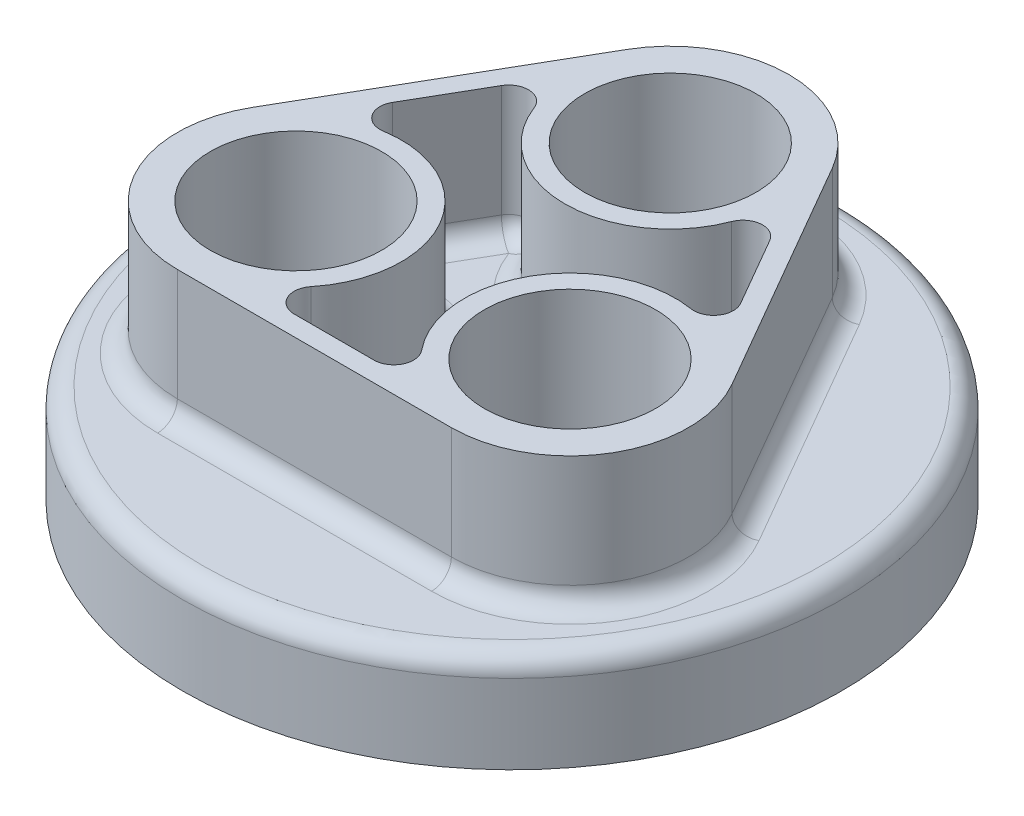
SolidWorks part; units mm, degrees
ref_plane "Front Plane" through (0, 0, 0) normal (0, 0, 1) x (1, 0, 0)
ref_plane "Top Plane" through (0, 0, 0) normal (0, 1, 0) x (1, 0, 0)
ref_plane "Right Plane" through (0, 0, 0) normal (1, 0, 0) x (0, 0, -1)
sketch "Sketch1" plane through (0, 0, 0) normal (0, 1, 0) x (1, 0, 0)
  circle A0 centre (0, 0) radius 50
  dimension "D1" = 100
extrude "Boss-Extrude1" add sketch "Sketch1" along normal blind 15
shell "Shell1" thickness 3 removed face at (0, 0, 50)
sketch "Sketch2" plane through (0, 15, 0) normal (0, 1, 0) x (1, 0, 0)
  line L0 (0, 5.7923) -> (0, 25.3037) construction
  line L1 (-15.5885, 33) -> (-36.3731, -3)
  line L2 (-20.7846, -30) -> (20.7846, -30)
  line L3 (-20.3558, 18.7426) -> (-26.4095, 8.2574)
  line L4 (6.0537, -27) -> (-6.0537, -27)
  line L5 (20.3558, 18.7426) -> (26.4095, 8.2574)
  line L6 (15.5885, 33) -> (36.3731, -3)
  arc A0 (15.5885, 33) -> (-15.5885, 33) centre (0, 24) ccw
  arc A1 (-36.3731, -3) -> (-20.7846, -30) centre (-20.7846, -12) ccw
  circle A2 centre (0, 0) radius 24 construction
  circle A3 centre (0, 24) radius 13
  circle A4 centre (20.7846, -12) radius 13
  circle A5 centre (-20.7846, -12) radius 13
  arc A6 (-23.3335, 3.7957) -> (-8.3796, -22.1053) centre (-20.7846, -12) cw
  arc A7 (-14.9539, 18.3096) -> (14.9539, 18.3096) centre (0, 24) ccw
  arc A8 (-6.0537, -27) -> (-8.3796, -22.1053) centre (-6.0537, -24) cw
  arc A9 (-20.3558, 18.7426) -> (-14.9539, 18.3096) centre (-17.7578, 17.2426) cw
  arc A10 (-26.4095, 8.2574) -> (-23.3335, 3.7957) centre (-23.8115, 6.7574) ccw
  arc A11 (20.3558, 18.7426) -> (14.9539, 18.3096) centre (17.7578, 17.2426) ccw
  arc A12 (26.4095, 8.2574) -> (23.3335, 3.7957) centre (23.8115, 6.7574) cw
  arc A13 (23.3335, 3.7957) -> (8.3796, -22.1053) centre (20.7846, -12) ccw
  arc A14 (6.0537, -27) -> (8.3796, -22.1053) centre (6.0537, -24) ccw
  arc A15 (36.3731, -3) -> (20.7846, -30) centre (20.7846, -12) cw
  point P21 (0, 0)
  point P26 (0, 0)
  point P27 (-15.6086, 26.6427)
  point P28 (0, 0)
  point P35 (0, 0)
  point P44 (0, -27)
  point P45 (0, -30)
  dimension "D1" = 18
  dimension "D2" = 18
  dimension "D3" = 48
  dimension "D4" = 26
  dimension "D8" = 3
  dimension "D9" = 3
  dimension "D10" = 3
  dimension "D6" = 3
  dimension "D7" = 3
  dimension "D5" = 3
extrude "Boss-Extrude2" add sketch "Sketch2" along normal blind 20
extrude "Cut-Extrude1" cut sketch "Sketch2<2>" against normal through all contours A5 | A3 | A4 region at (0, 15, -24) region at (20.7846, 15, 12) region at (-20.7846, 15, 12)
sketch "Sketch2<2>" plane through (0, 15, 0) normal (0, 1, 0) x (1, 0, 0) same geometry as "Sketch2"
sketch "Sketch3" plane through (0, 12, 0) normal (0, -1, 0) x (1, 0, 0)
  circle A0 centre (0, -24) radius 13 construction
  circle A1 centre (20.7846, 12) radius 13 construction
  circle A2 centre (-20.7846, 12) radius 13 construction
  circle A3 centre (0, -24) radius 13
  circle A4 centre (20.7846, 12) radius 13
  circle A5 centre (-20.7846, 12) radius 13
  circle A6 centre (-20.7846, 12) radius 16
  circle A7 centre (20.7846, 12) radius 16
  circle A8 centre (0, -24) radius 16
  dimension "D1" = 3
extrude "Boss-Extrude3" add sketch "Sketch3" along normal up to surface (12 mm away) up to face at (0, 0, 47)
fillet "Fillet1" radius 3 23 edges at (26.2814, 15, -5.0545) (6.9282, 15, 4) (8.7633, 15, 25.2876) (0, 15, 27) (-8.7633, 15, 25.2876) (-6.9282, 15, 4) (-26.2814, 15, -5.0545) (-23.3827, 15, -13.5) (-17.518, 15, -20.2331) (0, 15, -8) (17.518, 15, -20.2331) (36.3731, 15, 21) (0, 15, 30) (-36.3731, 15, 21) (-25.9808, 15, -15) (0, 15, -42) (23.3827, 15, -13.5) (25.9808, 15, -15) (0, 15, 50) (0, 12, 47) (20.7846, 12, 28) (-20.7846, 12, 28) (0, 12, -8)
